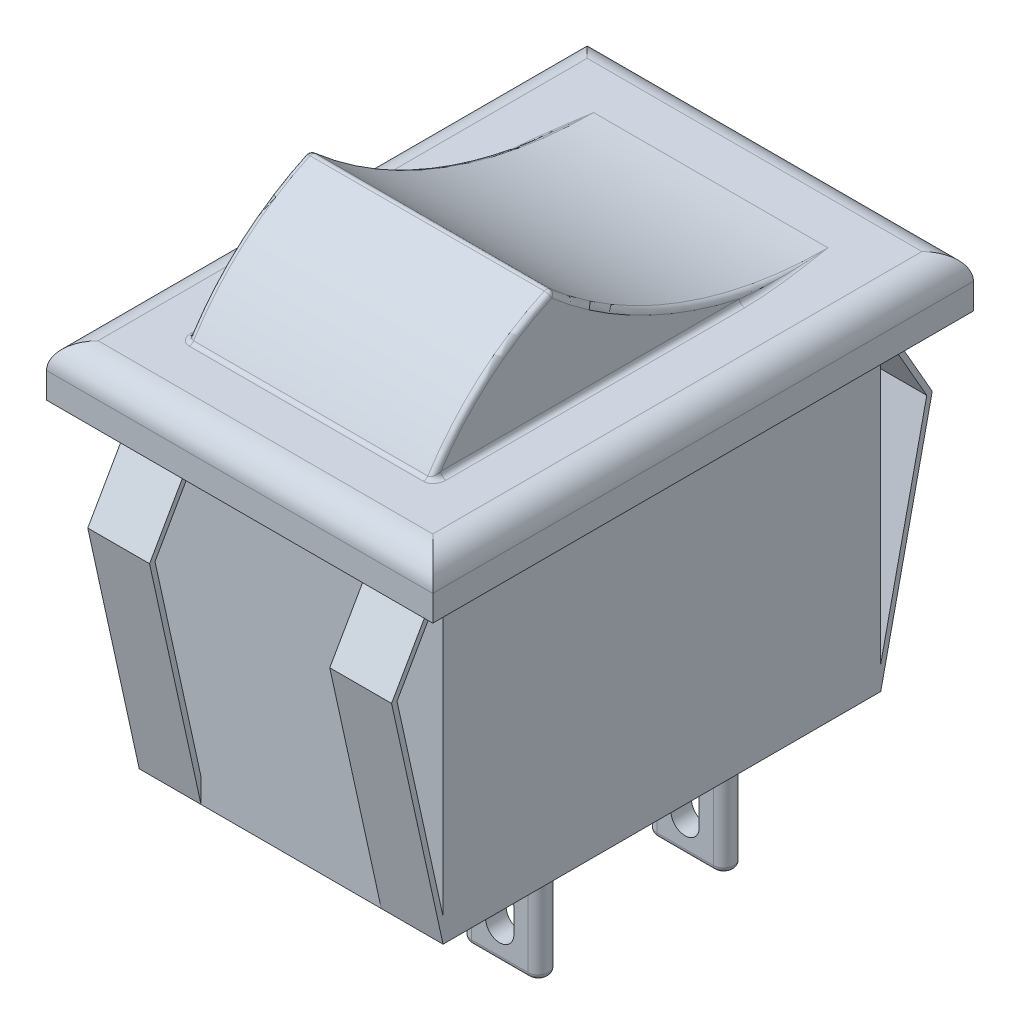
SolidWorks part; units mm, degrees
ref_plane "Plano frontal" through (0, 0, 0) normal (0, 0, 1) x (1, 0, 0)
ref_plane "Plano superior" through (0, 0, 0) normal (0, 1, 0) x (1, 0, 0)
ref_plane "Plano direito" through (0, 0, 0) normal (1, 0, 0) x (0, 0, -1)
sketch "Esboço1" plane through (0, 0, 0) normal (0, 1, 0) x (1, 0, 0)
  line L1 (-7.5, -10.5) -> (7.5, -10.5)
  line L2 (-7.5, -10.5) -> (-7.5, 10.5)
  line L3 (-7.5, 10.5) -> (7.5, 10.5)
  line L4 (7.5, -10.5) -> (7.5, 10.5)
  line L5 (-7.5, -10.5) -> (7.5, 10.5) construction
  line L6 (-7.5, 10.5) -> (7.5, -10.5) construction
  point P0 (0, 0)
  dimension "D1" = 21
  dimension "D2" = 15
extrude "Ressalto-extrusão1" add sketch "Esboço1" along normal blind 2
sketch "Esboço3" plane through (0, 0, 0) normal (1, 0, 0) x (0, 0, -1)
  line L0 (-7.8, 2) -> (7.8, 2)
  line L1 (-10.5, 2) -> (10.5, 2) construction
  arc A1 (-3.1, 6.11) -> (7.8, 2) centre (7.8, 18.5088) ccw
  arc A2 (-7.8, 2) -> (-3.1, 6.11) centre (1.1469, -3.4889) cw
  point P5 (0, 2)
  dimension "D1" = 15.6
  dimension "D2" = 4.7
  dimension "D3" = 4.11
extrude "Ressalto-extrusão2" add sketch "Esboço3" along normal mid plane 9.5
sketch "Esboço4" plane through (0, 0, 0) normal (0, -1, 0) x (1, 0, 0)
  line L1 (-5.9, -8.5) -> (5.9, -8.5)
  line L2 (-5.9, -8.5) -> (-5.9, 8.5)
  line L3 (-5.9, 8.5) -> (5.9, 8.5)
  line L4 (5.9, -8.5) -> (5.9, 8.5)
  line L5 (-5.9, -8.5) -> (5.9, 8.5) construction
  line L6 (-5.9, 8.5) -> (5.9, -8.5) construction
  point P0 (0, 0)
  dimension "D1" = 17
  dimension "D2" = 11.8
extrude "Ressalto-extrusão3" add sketch "Esboço4" along normal blind 12.6
sketch "Esboço5" plane through (-5.9, 0, 0) normal (-1, 0, 0) x (0, 0, 1)
  line L0 (-8.5, -12.6) -> (-10.5, -3.5)
  line L1 (-10.5, -3.5) -> (-8.5, 0)
  line L2 (-8.5, -0.4031) -> (-10.2881, -3.5323)
  line L3 (-8.5, -12.6) -> (-8.5, 0) construction
  line L4 (-10.2881, -3.5323) -> (-8.5, -11.6683)
  line L5 (-8.5, -11.6683) -> (-8.5, -12.6)
  line L6 (-8.5, -0.4031) -> (-8.5, 0)
  line L7 (-10.5, 0) -> (10.5, 0) construction
  line L8 (0, -8.25) -> (0, 8.25) construction
  line L9 (10.2881, -3.5323) -> (8.5, -11.6683)
  line L10 (8.5, -12.6) -> (10.5, -3.5)
  line L11 (8.5, -0.4031) -> (10.2881, -3.5323)
  line L12 (10.5, -3.5) -> (8.5, 0)
  line L13 (8.5, 0) -> (8.5, -0.4031)
  line L14 (8.5, -11.6683) -> (8.5, -12.6)
  dimension "D1" = 0.2
  dimension "D2" = 0.2
  dimension "D3" = 3.5
  dimension "D4" = 21
extrude "Ressalto-extrusão4" add sketch "Esboço5" against normal blind 2.4
mirror "Espelhar1" about plane through (0, 0, 0) normal (1, 0, 0) of "Ressalto-extrusão4"
sketch "Esboço6" plane through (0, -12.6, 0) normal (0, -1, 0) x (1, 0, 0)
  line L1 (-5.05, -4.5) -> (5.05, -4.5)
  line L2 (-5.05, -4.5) -> (-5.05, 4.5)
  line L3 (-5.05, 4.5) -> (5.05, 4.5)
  line L4 (5.05, -4.5) -> (5.05, 4.5)
  line L5 (-5.05, -4.5) -> (5.05, 4.5) construction
  line L6 (-5.05, 4.5) -> (5.05, -4.5) construction
  point P0 (0, 0)
  dimension "D1" = 9
  dimension "D2" = 10.1
extrude "Ressalto-extrusão5" add sketch "Esboço6" along normal blind 0.8
sketch "Esboço7" plane through (0, -13.4, 0) normal (0, -1, 0) x (1, 0, 0)
  line L0 (-1.1, 0) -> (1.1, 0) construction
  line L1 (-1.1, 0.4) -> (1.1, 0.4)
  line L2 (-1.1, -0.4) -> (1.1, -0.4)
  line L3 (-1.1, -7.2) -> (1.1, -7.2) construction
  line L12 (-1.1, -6.8) -> (1.1, -6.8)
  line L13 (-1.1, -7.6) -> (1.1, -7.6)
  arc A0 (-1.1, 0.4) -> (-1.1, -0.4) centre (-1.1, 0) ccw
  arc A1 (1.1, -0.4) -> (1.1, 0.4) centre (1.1, 0) ccw
  arc A2 (-1.1, -6.8) -> (-1.1, -7.6) centre (-1.1, -7.2) ccw
  arc A3 (1.1, -7.6) -> (1.1, -6.8) centre (1.1, -7.2) ccw
  point P6 (0, 0)
  point P13 (0, -7.2)
  dimension "D2" = 3
  dimension "D3" = 0.8
  dimension "D4" = 8
  dimension "D5" = 0.8
extrude "Ressalto-extrusão6" add sketch "Esboço7" along normal blind 6.8 and the other way up to next
sketch "Esboço8" plane through (0, 0, -7.6) normal (0, 0, -1) x (-1, 0, 0)
  line L0 (0, -19) -> (0, -18.1) construction
  line L1 (-0.55, -19) -> (-0.55, -18.1)
  line L2 (0.55, -19) -> (0.55, -18.1)
  line L3 (1.1, -20.2) -> (-1.1, -20.2) construction
  arc A0 (-0.55, -19) -> (0.55, -19) centre (0, -19) ccw
  arc A1 (0.55, -18.1) -> (-0.55, -18.1) centre (0, -18.1) ccw
  point P3 (0, -18.55)
  dimension "D2" = 2
  dimension "D3" = 1.2
  dimension "D1" = 1.1
extrude "Corte-extrusão1" cut sketch "Esboço8" against normal through all
fillet "Filete1" radius 0.2 16 edges at (4.75, 2, 0) (-4.75, 2, 0) (4.75, 4.4126, 5.7627) (0, 2, 7.8) (-4.75, 4.4126, 5.7627) (4.75, 3.0616, -1.9754) (0, 6.11, 3.1) (-4.75, 3.0616, -1.9754) (0, -20.2, 0.4) (1.5, -20.2, 0) (0, -20.2, -0.4) (-1.5, -20.2, 0) (0, -20.2, -6.8) (1.5, -20.2, -7.2) (0, -20.2, -7.6) (-1.5, -20.2, -7.2)
fillet "Filete2" radius 1 4 edges at (0, 2, 10.5) (-7.5, 2, 0) (7.5, 2, 0) (0, 2, -10.5)
